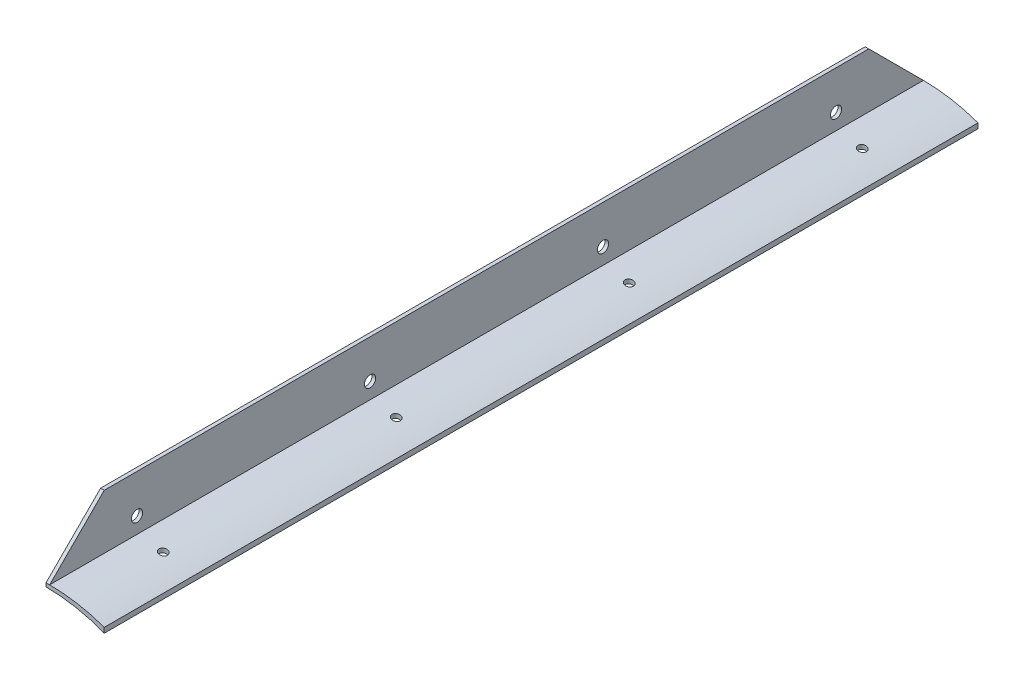
SolidWorks part; units mm, degrees
material "6061-T6 (SS)"
ref_plane "Front Plane" through (0, 0, 0) normal (0, 0, 1) x (1, 0, 0)
ref_plane "Top Plane" through (0, 0, 0) normal (0, 1, 0) x (1, 0, 0)
ref_plane "Right Plane" through (0, 0, 0) normal (1, 0, 0) x (0, 0, -1)
sketch "Sketch1" plane through (0, 0, 0) normal (0, 0, 1) x (1, 0, 0)
  line L0 (0, 0) -> (0, 25.4)
  line L1 (0, 25.4) -> (1.5875, 25.4)
  line L2 (1.5875, 25.4) -> (1.5875, 1.5875)
  line L3 (25.4, -2.5468) -> (25.4, -4.7819)
  arc A0 (0, 0) -> (25.4, -4.7819) centre (0, -69.85) cw
  arc A1 (1.5875, 1.5875) -> (25.4, -2.5468) centre (1.5875, -69.0562) cw
  dimension "D1" = 25.4
  dimension "D5" = 69.85
  dimension "D6" = 70.6437
  dimension "D2" = 23.8125
  dimension "D3" = 1.5875
  dimension "D4" = 25.4
extrude "Extrude1" add sketch "Sketch1" along normal mid plane 381
ref_plane "Plane2" through (0, 0, 0) normal (0, 0, -1) x (-1, 0, 0)
sketch "Sketch2" plane through (0, 0, 0) normal (-1, 0, 0) x (0, 0, 1)
  line L0 (190.5, 25.4) -> (166.6875, 25.4)
  line L1 (190.5, 25.4) -> (-190.5, 25.4) construction
  line L2 (166.6875, 25.4) -> (190.5, 1.5875)
  line L3 (190.5, 25.4) -> (190.5, 0) construction
  line L4 (190.5, 1.5875) -> (190.5, 25.4)
  dimension "D1" = 1.5875
extrude "Extrude2" cut sketch "Sketch2" against normal blind 387.35
mirror "Mirror2" about plane through (0, 0, 0) normal (0, 0, -1) of "Extrude2"
ref_plane "Plane3" through (0, 1.5875, 0) normal (0, 1, 0) x (-1, 0, 0)
sketch "Sketch3" plane through (0, 1.5875, 0) normal (0, 1, 0) x (-1, 0, 0)
  line L0 (-1.5875, -152.4) -> (-13.0175, -152.4) construction
  line L1 (-1.5875, 166.6875) -> (-1.5875, -166.6875) construction
  line L2 (-25.4, -190.5) -> (-1.5875, -190.5) construction
  dimension "D1" = 11.43
  dimension "D2" = 38.1
hole_wizard "#6 Clearance Hole1" positions "Sketch6" profile "Sketch7" hole size "#6" standard "Ansi Inch" end condition through all
sketch "Sketch6" plane through (0, 1.5875, 0) normal (0, 1, 0) x (-1, 0, 0)
  point P1 (-13.0175, -152.4)
sketch "Sketch7" plane through (13.0175, 1.5875, -152.4) normal (1, 0, 0) x (0, 0, 1)
  line L0 (0, 0) -> (0, 6.3694)
  line L1 (0, 6.3694) -> (1.8288, 6.3694)
  line L2 (1.8288, 6.3694) -> (1.8288, 0)
  line L5 (1.8288, 0) -> (0, 0)
  line L11 (0, -6.35) -> (0, 107.95) construction
  dimension "Thru Hole Dia." = 3.6576
  dimension "Thru Hole Depth" = 6.3694
sketch "Sketch8" plane through (1.5875, 0, 0) normal (1, 0, 0) x (0, 0, -1)
  line L0 (152.4, 1.5875) -> (152.4, 8.5725) construction
  dimension "D1" = 6.985
hole_wizard "#10 (0.1935) Diameter Hole1" positions "3DSketch2" profile "Sketch10" hole size "#10" standard "Ansi Inch" end condition through all
sketch3d "3DSketch2"
  point P0 (1.5875, 8.5725, -152.4)
sketch "Sketch10" plane through (1.5875, 8.5725, -152.4) normal (0, 1, 0) x (0, 0, -1)
  line L0 (0, 0) -> (0, 1.5875)
  line L1 (0, 1.5875) -> (2.4574, 1.5875)
  line L2 (2.4574, 1.5875) -> (2.4574, 0)
  line L5 (2.4574, 0) -> (0, 0)
  line L11 (0, -6.35) -> (0, 107.95) construction
  dimension "Thru Hole Dia." = 4.9149
  dimension "Thru Hole Depth" = 1.5875
pattern_linear "LPattern1" count 4 spacing 101.6 along (0, 0, 1) of "#10 (0.1935) Diameter Hole1", "#6 Clearance Hole1"
